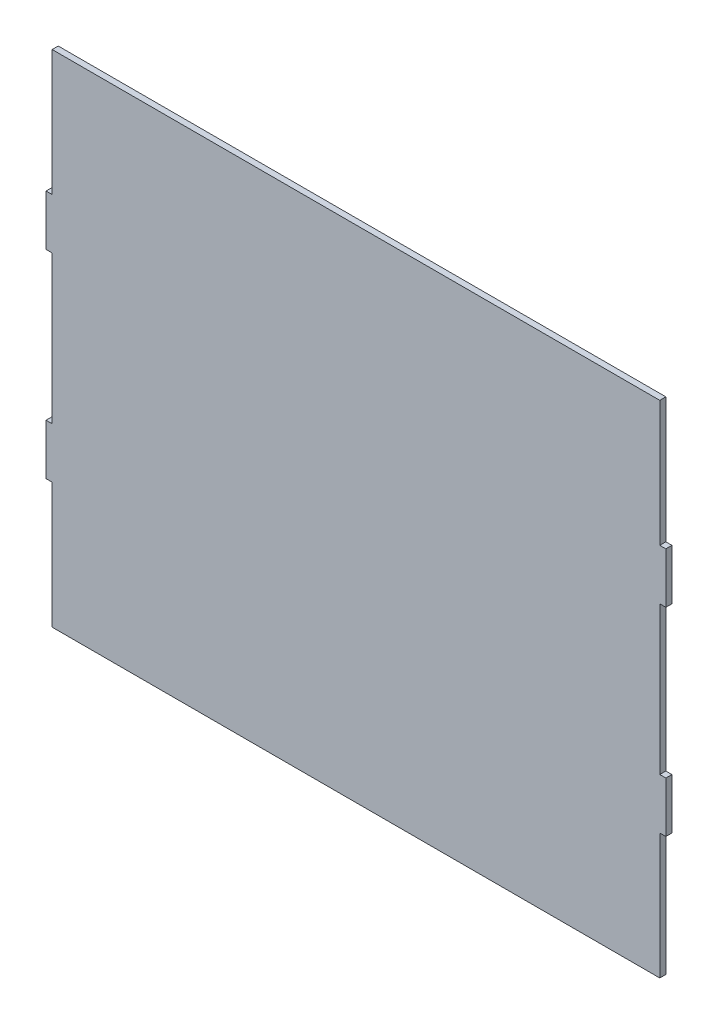
SolidWorks part; units mm, degrees
material "Maple"
ref_plane "Front Plane" through (0, 0, 0) normal (0, 0, 1) x (1, 0, 0)
ref_plane "Top Plane" through (0, 0, 0) normal (0, 1, 0) x (1, 0, 0)
ref_plane "Right Plane" through (0, 0, 0) normal (1, 0, 0) x (0, 0, -1)
sketch "Sketch1" plane through (0, 0, 0) normal (0, 0, 1) x (1, 0, 0)
  line L1 (-300, 247) -> (300, 247)
  line L2 (-300, 247) -> (-300, 123)
  line L3 (-300, -247) -> (300, -247)
  line L4 (300, 247) -> (300, 123)
  line L5 (-300, 247) -> (300, -247) construction
  line L6 (-300, -247) -> (300, 247) construction
  line L7 (-306, 123) -> (-300, 123)
  line L8 (-306, 123) -> (-306, 73)
  line L9 (-306, 73) -> (-300, 73)
  line L11 (-300, 189) -> (-282.5, 164) construction
  line L12 (-300, -123) -> (-300, -247)
  line L13 (0, 247) -> (0, -247) construction
  line L14 (306, 73) -> (300, 73)
  line L15 (306, 123) -> (306, 73)
  line L16 (306, 123) -> (300, 123)
  line L24 (-300, 73) -> (-300, -73)
  line L31 (-306, -123) -> (-300, -123)
  line L33 (300, -247) -> (300, -123)
  line L34 (300, -123) -> (306, -123)
  line L35 (-306, -123) -> (-306, -73)
  line L36 (-306, -73) -> (-300, -73)
  line L38 (300, 73) -> (300, -73)
  line L39 (300, -73) -> (306, -73)
  line L40 (306, -73) -> (306, -123)
  point P0 (0, 0)
  point P6 (-300, 189)
  point P31 (-156.1598, -207)
  dimension "D1" = 600
  dimension "D2" = 146
  dimension "1" = 124
  dimension "D4" = 124
  dimension "D5" = 50
  dimension "D6" = 6
  dimension "D7" = 124
  dimension "D8" = 6
  dimension "D9" = 50
  dimension "D10" = 6
  dimension "D11" = 50
  dimension "D12" = 50
  dimension "D13" = 124
  dimension "D14" = 146
  dimension "D15" = 494
extrude "Boss-Extrude1" add sketch "Sketch1" along normal blind 6
